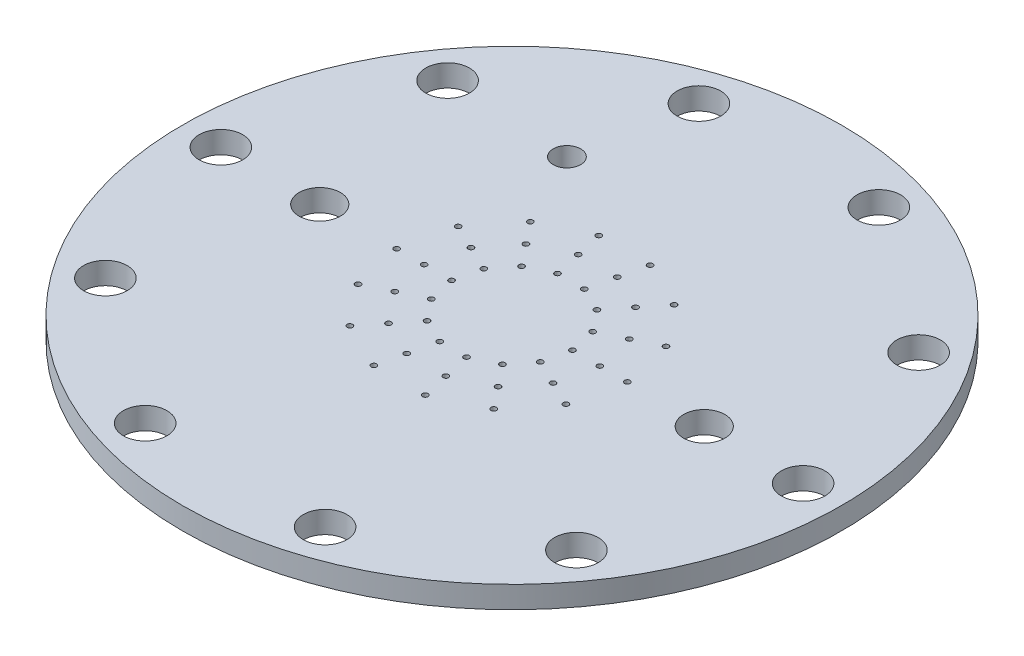
SolidWorks part; units mm, degrees
ref_plane "Front Plane" through (0, 0, 0) normal (0, 0, 1) x (1, 0, 0)
ref_plane "Top Plane" through (0, 0, 0) normal (0, 1, 0) x (1, 0, 0)
ref_plane "Right Plane" through (0, 0, 0) normal (1, 0, 0) x (0, 0, -1)
sketch "Sketch1" plane through (0, 0, 0) normal (0, 0, 1) x (1, 0, 0)
  line L0 (0, 0) -> (0, -5.08)
  line L2 (76.2, -5.08) -> (76.2, 0)
  line L3 (76.2, 0) -> (0, 0)
  line L4 (0, -5.08) -> (54.8259, -5.08)
  line L5 (54.8259, -5.08) -> (54.8259, -2.3876)
  line L6 (54.8259, -2.3876) -> (58.8899, -2.3876)
  line L7 (58.8899, -2.3876) -> (58.8899, -5.08)
  line L8 (58.8899, -5.08) -> (76.2, -5.08)
  dimension "D1" = 5.08
  dimension "D2" = 76.2
  dimension "D3" = 58.8899
  dimension "D4" = 4.064
  dimension "D5" = 2.6924
revolve "Revolve1" add sketch "Sketch1" angle 360 about L0
ref_axis "Axis1" through (0, -5.334, 0) along (0, 1, 0)
sketch "Sketch2" plane through (0, 0, 0) normal (0, 1, 0) x (1, 0, 0)
  line L0 (0, 0) -> (67.31, 0) construction
  dimension "D1" = 67.31
hole_wizard "3/8 Clearance Hole1" positions "3DSketch2" profile "Sketch3" hole size "3/8" standard "ANSI Inch" end condition through all
sketch3d "3DSketch2"
  point P0 (67.31, 0, 0)
sketch "Sketch3" plane through (67.31, 0, 0) normal (1, 0, 0) x (0, 0, 1)
  line L0 (0, 0) -> (0, 5.08)
  line L1 (0, 5.08) -> (5.0419, 5.08)
  line L2 (5.0419, 5.08) -> (5.0419, 0)
  line L5 (5.0419, 0) -> (0, 0)
  line L11 (0, -6.35) -> (0, 107.95) construction
  dimension "Thru Hole Dia." = 10.0838
  dimension "Thru Hole Depth" = 5.08
pattern_circular "CirPattern1" count 10 over 360 about axis through (0, -5.334, 0) along (0, 1, 0) of "3/8 Clearance Hole1"
hole_wizard "3/8 (0.375) Diameter Hole1" positions "3DSketch3" profile "Sketch4" hole size "3/8" standard "ANSI Inch" end condition through all
sketch3d "3DSketch3"
  line L1 (0, 0, 0) -> (67.31, 0, 0) construction
  point P18 (44.45, 0, 0)
  point P38 (-44.45, 0, 0)
  dimension "D1" = 44.45
  dimension "D2" = 44.45
sketch "Sketch4" plane through (44.45, 0, 0) normal (1, 0, 0) x (0, 0, 1)
  line L0 (0, 0) -> (0, 5.08)
  line L1 (0, 5.08) -> (4.7625, 5.08)
  line L2 (4.7625, 5.08) -> (4.7625, 0)
  line L5 (4.7625, 0) -> (0, 0)
  line L11 (0, -6.35) -> (0, 107.95) construction
  dimension "Thru Hole Dia." = 9.525
  dimension "Thru Hole Depth" = 5.08
sketch "Sketch5" plane through (0, 0, 0) normal (0, 1, 0) x (1, 0, 0)
  line L0 (0, 0) -> (0, 38.1) construction
  line L1 (0, 38.1) -> (0, 0) construction
  line L2 (0, 0) -> (-25.4, 38.1) construction
  line L3 (-25.4, 38.1) -> (0, 38.1) construction
  dimension "D1" = 38.1
  dimension "D2" = 25.4
hole_wizard "1/4 (0.25) Diameter Hole1" positions "3DSketch4" profile "Sketch6" hole size "1/4" standard "ANSI Inch" end condition through all
sketch3d "3DSketch4"
  point P0 (-25.4, 0, -38.1)
sketch "Sketch6" plane through (-25.4, 0, -38.1) normal (1, 0, 0) x (0, 0, 1)
  line L0 (0, 0) -> (0, 5.08)
  line L1 (0, 5.08) -> (3.175, 5.08)
  line L2 (3.175, 5.08) -> (3.175, 0)
  line L5 (3.175, 0) -> (0, 0)
  line L11 (0, -6.35) -> (0, 107.95) construction
  dimension "Thru Hole Dia." = 6.35
  dimension "Thru Hole Depth" = 5.08
sketch "Sketch7" plane through (0, 0, 0) normal (0, 1, 0) x (1, 0, 0)
  line L0 (0, 0) -> (67.31, 0) construction
  circle A0 centre (0, 0) radius 30.988 construction
  circle A1 centre (13.97, 0) radius 0.635
  circle A2 centre (20.32, 0) radius 0.635
  circle A3 centre (26.67, 0) radius 0.635
  circle A4 centre (12.5865, -6.0614) radius 0.635
  circle A5 centre (18.3077, -8.8165) radius 0.635
  circle A6 centre (24.0288, -11.5717) radius 0.635
  circle A7 centre (8.7102, -10.9222) radius 0.635
  circle A8 centre (12.6693, -15.8868) radius 0.635
  circle A9 centre (16.6285, -20.8514) radius 0.635
  circle A10 centre (3.1086, -13.6197) radius 0.635
  circle A11 centre (4.5216, -19.8105) radius 0.635
  circle A12 centre (5.9346, -26.0013) radius 0.635
  circle A13 centre (-3.1086, -13.6197) radius 0.635
  circle A14 centre (-4.5216, -19.8105) radius 0.635
  circle A15 centre (-5.9346, -26.0013) radius 0.635
  circle A16 centre (-8.7102, -10.9222) radius 0.635
  circle A17 centre (-12.6693, -15.8868) radius 0.635
  circle A18 centre (-16.6285, -20.8514) radius 0.635
  circle A19 centre (-12.5865, -6.0614) radius 0.635
  circle A20 centre (-18.3077, -8.8165) radius 0.635
  circle A21 centre (-24.0288, -11.5717) radius 0.635
  circle A22 centre (-13.97, 0) radius 0.635
  circle A23 centre (-20.32, 0) radius 0.635
  circle A24 centre (-26.67, 0) radius 0.635
  circle A25 centre (-12.5865, 6.0614) radius 0.635
  circle A26 centre (-18.3077, 8.8165) radius 0.635
  circle A27 centre (-24.0288, 11.5717) radius 0.635
  circle A28 centre (-8.7102, 10.9222) radius 0.635
  circle A29 centre (-12.6693, 15.8868) radius 0.635
  circle A30 centre (-16.6285, 20.8514) radius 0.635
  circle A31 centre (-3.1086, 13.6197) radius 0.635
  circle A32 centre (-4.5216, 19.8105) radius 0.635
  circle A33 centre (-5.9346, 26.0013) radius 0.635
  circle A34 centre (3.1086, 13.6197) radius 0.635
  circle A35 centre (4.5216, 19.8105) radius 0.635
  circle A36 centre (5.9346, 26.0013) radius 0.635
  circle A37 centre (8.7102, 10.9222) radius 0.635
  circle A38 centre (12.6693, 15.8868) radius 0.635
  circle A39 centre (16.6285, 20.8514) radius 0.635
  circle A40 centre (12.5865, 6.0614) radius 0.635
  circle A41 centre (18.3077, 8.8165) radius 0.635
  circle A42 centre (24.0288, 11.5717) radius 0.635
  point P91 (0, 0)
  dimension "D1" = 61.976
  dimension "D2" = 1.27
  dimension "D6" = 1.27
  dimension "D7" = 1.27
  dimension "D3" = 13.97
  dimension "D4" = 6.35
  dimension "D5" = 6.35
  dimension "D8" = 14
extrude "Cut-Extrude1" cut sketch "Sketch7" against normal blind 2.54
